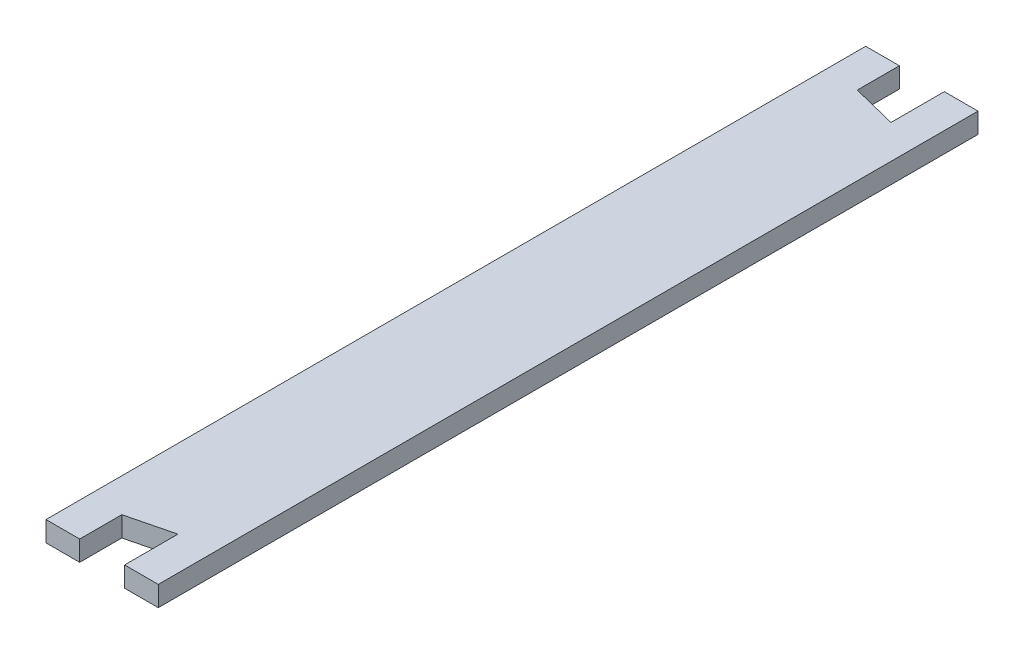
SolidWorks part; units mm, degrees
ref_plane "Front Plane" through (0, 0, 0) normal (0, 0, 1) x (1, 0, 0)
ref_plane "Top Plane" through (0, 0, 0) normal (0, 1, 0) x (1, 0, 0)
ref_plane "Right Plane" through (0, 0, 0) normal (1, 0, 0) x (0, 0, -1)
sketch "Sketch1" plane through (0, 0, 0) normal (0, 1, 0) x (1, 0, 0)
  line L0 (-450, 300) -> (-400, 300)
  line L1 (-400, 300) -> (-200, 250)
  line L2 (-200, 250) -> (200, 250) construction
  line L3 (200, 250) -> (600, 40) construction
  line L4 (600, 40) -> (1200, 40)
  line L5 (-450, -300) -> (-400, -300)
  line L6 (-400, -300) -> (-200, -250)
  line L7 (-200, -250) -> (200, -250) construction
  line L8 (200, -250) -> (600, -40) construction
  line L9 (600, -40) -> (1200, -40)
  line L10 (600, 40) -> (600, -40) construction
  line L11 (200, -250) -> (200, 250) construction
  line L12 (-200, 250) -> (-200, -250) construction
  line L13 (-400, -300) -> (-400, 300) construction
  line L14 (0, 0) -> (200, 0) construction
  line L15 (0, 250) -> (0, 0) construction
  line L16 (1200, 40) -> (1200, -40)
  line L17 (-450, 300) -> (-450, -300)
  line L18 (600, 0) -> (200, 0) construction
  line L19 (-450, 0) -> (-400, 0) construction
  line L20 (-400, 0) -> (-200, 0) construction
  line L21 (-200, 0) -> (0, 0) construction
  line L22 (-200, 250) -> (600, 40)
  line L23 (600, -40) -> (-200, -250)
  dimension "D1" = 600
  dimension "D2" = 200
  dimension "D3" = 50
  dimension "D4" = 400
  dimension "D5" = 500
  dimension "D6" = 80
  dimension "D7" = 600
  dimension "D8" = 400
extrude "Boss-Extrude1" add sketch "Sketch1" along normal blind 15
sketch "Sketch2" plane through (0, 0, 0) normal (0, 0, 1) x (1, 0, 0)
  line L0 (-450, 0) -> (-450, -40)
  line L1 (-450, -40) -> (-400, -40)
  line L2 (-400, -40) -> (-400, 0)
  line L3 (-400, 0) -> (-200, 0) construction
  line L4 (-400, 0) -> (-450, 0)
  line L5 (-440, -15) -> (-440, -40)
  line L6 (-410, -15) -> (-410, -40)
  line L7 (-425, 0) -> (-425, -15) construction
  circle A0 centre (-425, -15) radius 15
  dimension "D1" = 30
  dimension "D2" = 40
extrude "Boss-Extrude2" add sketch "Sketch2" along normal up to surface and the other way up to surface contours L4 L7 A0 L6 L1 L2 | L7 L4 L0 L1 L5 A0 region at (-444.1006, -18.2067, 0) region at (-405.8994, -18.2067, 0) up to face at (-425, 7.5, 300) other way up to face at (-425, 7.5, -300)
sketch "Sketch4" plane through (0, 0, 0) normal (0, 1, 0) x (1, 0, 0)
  line L0 (-450, 230) -> (-400, 230)
  line L1 (-450, 300) -> (-450, -300) construction
  line L2 (-400, 230) -> (-150, 167.5)
  line L3 (-150, 167.5) -> (-150, -167.5)
  line L4 (-150, -167.5) -> (-400, -230)
  line L5 (-400, -230) -> (-450, -230)
  line L6 (-400, 230) -> (-400, -230) construction
  line L7 (-200, 250) -> (-200, -250) construction
  line L9 (-200, 0) -> (-150, 0) construction
  line L10 (-400, -230) -> (-400, -300) construction
  line L11 (-400, -300) -> (-200, -250) construction
  line L12 (-450, 230) -> (-450, -230)
  line L14 (-200, 250) -> (-400, 300) construction
  line L15 (-100, 155) -> (-100, -155)
  line L16 (-100, -155) -> (520, 0)
  line L17 (520, 0) -> (-100, 155)
  line L18 (520, 0) -> (-100, 0) construction
  dimension "D1" = 460
  dimension "D2" = 300
  dimension "D3" = 50
extrude "Cut-Extrude2" cut sketch "Sketch4" against normal through all both and the other way through all
sketch "Sketch5" plane through (0, 0, 0) normal (1, 0, 0) x (0, 0, -1)
  line L0 (-300, 0) -> (-230, 0) construction
  line L1 (-285, 0) -> (-245, 0)
  line L2 (-285, 0) -> (-285, -40)
  line L3 (-285, -40) -> (-245, -40)
  line L4 (-245, 0) -> (-245, -40)
  line L5 (-300, -40) -> (-230, -40) construction
  line L6 (230, 0) -> (300, 0) construction
  line L7 (245, 0) -> (285, 0)
  line L8 (245, 0) -> (245, -40)
  line L9 (245, -40) -> (285, -40)
  line L10 (285, 0) -> (285, -40)
  line L11 (230, -40) -> (300, -40) construction
  line L12 (-300, 0) -> (-300, -40) construction
  line L13 (230, -40) -> (230, 0) construction
  line L14 (300, 0) -> (300, -40) construction
  dimension "D1" = 15
  dimension "D2" = 15
  dimension "D3" = 15
  dimension "D4" = 15
extrude "Cut-Extrude3" cut sketch "Sketch5" against normal through all
sketch "Sketch7" plane through (1200, 0, 0) normal (1, 0, 0) x (0, 0, -1)
  line L1 (-40, 15) -> (-87.5, 50)
  line L2 (-87.5, 50) -> (-87.5, 88.7)
  line L3 (-87.5, 88.7) -> (87.5, 88.7)
  line L4 (87.5, 88.7) -> (87.5, 50)
  line L5 (87.5, 50) -> (40, 15)
  line L7 (-40, 15) -> (40, 15)
  line L8 (-20, 50) -> (-20, 88.7)
  line L9 (87.5, 50) -> (-87.5, 50) construction
  line L10 (0, 88.7) -> (0, 50) construction
  line L11 (-20, 88.7) -> (20, 88.7)
  line L12 (0, 50) -> (0, 0) construction
  line L13 (20, 88.7) -> (20, 50)
  line L14 (-73, 88.7) -> (-63, 88.7)
  line L15 (-73, 88.7) -> (-73, 63.2)
  line L16 (-73, 63.2) -> (-63, 63.2)
  line L17 (-63, 88.7) -> (-63, 63.2)
  line L18 (48.5, 88.7) -> (58.5, 88.7)
  line L19 (48.5, 88.7) -> (48.5, 63.2)
  line L20 (48.5, 63.2) -> (58.5, 63.2)
  line L21 (58.5, 88.7) -> (58.5, 63.2)
  circle A0 centre (0, 50) radius 20
  line M14 (40, 15) -> (-40, 15)
  dimension "D3" = 40
  dimension "D1" = 175
  dimension "D2" = 50
  dimension "D4" = 25.5
  dimension "D5" = 10
  dimension "D6" = 63
  dimension "D7" = 48.5
  dimension "D8" = 38.7
extrude "Boss-Extrude4" add sketch "Sketch7" against normal blind 75 contours L3 L21 L20 L19 L17 L16 L15 L2 L1 L5 L4 M14 region at (1200, 34.0287, 62.6236)
sketch "Sketch8" plane through (0, 0, 0) normal (0, 0, 1) x (1, 0, 0)
  line L0 (1125, 88.7) -> (1200, 88.7) construction
  line L1 (1140, 88.7) -> (1185, 88.7)
  line L2 (1140, 88.7) -> (1140, 15)
  line L3 (1140, 15) -> (1185, 15)
  line L4 (1185, 88.7) -> (1185, 15)
  line L5 (1125, 15) -> (1200, 15) construction
  line L6 (1125, 50) -> (1125, 88.7) construction
  line L7 (1200, 50) -> (1200, 88.7) construction
  line L8 (1155, 88.7) -> (1170, 88.7) construction
  line L9 (1155, 88.7) -> (1170, 88.7)
  line L10 (1155, 88.7) -> (1155, 15)
  line L11 (1155, 15) -> (1170, 15)
  line L12 (1170, 88.7) -> (1170, 15)
  line L15 (1162.5, 50) -> (1162.5, 88.7) construction
  line L16 (1125, 50) -> (1200, 50) construction
  line L17 (1155, 88.7) -> (1170, 88.7) construction
  dimension "D1" = 15
  dimension "D2" = 15
  dimension "D3" = 15
extrude "Cut-Extrude4" cut sketch "Sketch8" against normal through all both and the other way through all contours L10 L1 L2 L3 | L1 L12 L3 L4 region at (1147.5, 51.85, 0) region at (1177.5, 51.85, 0)
fillet "Fillet1" radius 5 53 edges at (1192.5, 50, 87.5) (1162.5, 50, 87.5) (1132.5, 50, 87.5) (1192.5, 50, -87.5) (1162.5, 50, -87.5) (1132.5, 50, -87.5) (1192.5, 88.7, -87.5) (1162.5, 88.7, -87.5) (1132.5, 88.7, -87.5) (1132.5, 88.7, -58.5) (1162.5, 88.7, -58.5) (1192.5, 88.7, -58.5) (1192.5, 88.7, -48.5) (1162.5, 88.7, -48.5) (1132.5, 88.7, -48.5) (1192.5, 88.7, -20) (1162.5, 88.7, -20) (1132.5, 88.7, -20) (1192.5, 88.7, 63) (1162.5, 88.7, 63) (1132.5, 88.7, 63) (1132.5, 88.7, 87.5) (1162.5, 88.7, 87.5) (1192.5, 88.7, 87.5) (1192.5, 88.7, 73) (1162.5, 88.7, 73) (1132.5, 88.7, 73) (1192.5, 88.7, 20) (1162.5, 88.7, 20) (1132.5, 88.7, 20) (600, 7.5, 40) (600, 7.5, -40) (520, 7.5, 0) (-440, -40, -292.5) (-440, -40, -237.5) (-400, -40, -292.5) (-400, -40, -237.5) (-450, -40, -237.5) (-410, -40, -237.5) (-450, -40, -292.5) (-410, -40, -292.5) (-150, 7.5, 167.5) (-100, 7.5, 155) (-150, 7.5, -167.5) (-100, 7.5, -155) (-450, -40, 237.5) (-410, -40, 237.5) (-440, -40, 237.5) (-400, -40, 237.5) (-450, -40, 292.5) (-440, -40, 292.5) (-400, -40, 292.5) (-410, -40, 292.5)
sketch "Sketch9" plane through (0, 0, 0) normal (0, 1, 0) x (1, 0, 0)
  line L35 (-450, -300) -> (-400, -300) construction
  line L36 (-425, -300) -> (-425, -285) construction
  line L37 (-450, 0) -> (0, 0) construction
  line L38 (-437.5, -300) -> (-412.5, -300)
  line L39 (-437.5, -300) -> (-437.5, -285)
  line L56 (1140, -40) -> (1140, -85.466) construction
  line L57 (1200, -40) -> (1185, -40)
  line L58 (1200, -40) -> (1200, -25)
  line L59 (1200, -25) -> (1185, -25)
  line L60 (1185, -40) -> (1185, -25)
  line L61 (1200, 40) -> (1185, 40)
  line L62 (1200, 40) -> (1200, 25)
  line L63 (1200, 25) -> (1185, 25)
  line L64 (1185, 40) -> (1185, 25)
  line L65 (1170, 40) -> (1155, 40)
  line L66 (1170, 40) -> (1170, 25)
  line L67 (1170, 25) -> (1155, 25)
  line L68 (1155, 40) -> (1155, 25)
  line L69 (1140, 40) -> (1125, 40)
  line L70 (1140, 40) -> (1140, 25)
  line L71 (1140, 25) -> (1125, 25)
  line L72 (1125, 40) -> (1125, 25)
  line L73 (1125, -40) -> (1140, -40)
  line L74 (1125, -40) -> (1125, -25)
  line L75 (1125, -25) -> (1140, -25)
  line L76 (1140, -40) -> (1140, -25)
  line L77 (1155, -40) -> (1170, -40)
  line L78 (1155, -40) -> (1155, -25)
  line L79 (1155, -25) -> (1170, -25)
  line L80 (1170, -40) -> (1170, -25)
  line L81 (600.6453, -40) -> (1200, -40) construction
  line L82 (1200, 40) -> (600.6453, 40) construction
  line L83 (1140, 40) -> (1125, 40) construction
  line L84 (1125, 85.466) -> (1125, 40) construction
  line L85 (1140, -25) -> (1155, -25) construction
  line L86 (1170, -25) -> (1185, -25) construction
  line L87 (1185, 25) -> (1170, 25) construction
  line L88 (1155, 25) -> (1140, 25) construction
  line L89 (-437.5, -285) -> (-412.5, -285)
  line L90 (-412.5, -300) -> (-412.5, -285)
  line L92 (-410, -230) -> (-440, -230) construction
  line L93 (-437.5, -230) -> (-412.5, -230)
  line L94 (-437.5, -230) -> (-437.5, -245)
  line L95 (-437.5, -245) -> (-412.5, -245)
  line L96 (-412.5, -230) -> (-412.5, -245)
  line L97 (-425, -245) -> (-400, -245) construction
  line L98 (-425, -285) -> (-425, -245) construction
  line L99 (-425, 285) -> (-425, 245) construction
  line L100 (-425, 300) -> (-425, 285) construction
  line L101 (-450, 300) -> (-400, 300) construction
  line L102 (-412.5, 230) -> (-412.5, 245)
  line L103 (-437.5, 245) -> (-412.5, 245)
  line L104 (-437.5, 230) -> (-437.5, 245)
  line L105 (-437.5, 230) -> (-412.5, 230)
  line L106 (-412.5, 300) -> (-412.5, 285)
  line L107 (-437.5, 285) -> (-412.5, 285)
  line L108 (-437.5, 300) -> (-437.5, 285)
  line L109 (-437.5, 300) -> (-412.5, 300)
  dimension "D1" = 15
  dimension "D2" = 25
  dimension "D3" = 15
extrude "Cut-Extrude5" cut sketch "Sketch9" against normal through all both and the other way through all
sketch "Sketch10" plane through (0, 0, 0) normal (0, 0, 1) x (1, 0, 0)
  line L1 (-450, 15) -> (1200, 15)
  line L2 (-450, 15) -> (-450, 0)
  line L3 (-450, 0) -> (1200, 0)
  line L4 (1200, 15) -> (1200, 0)
  line L5 (-450, 15) -> (-450, -35) construction
  line L6 (-486.0808, 110.0266) -> (1242.84, 110.0266)
  line L7 (-486.0808, 110.0266) -> (-486.0808, -68.8272)
  line L8 (-486.0808, -68.8272) -> (1242.84, -68.8272)
  line L9 (1242.84, 110.0266) -> (1242.84, -68.8272)
  dimension "D1" = 15
extrude "Cut-Extrude6" cut sketch "Sketch10" against normal through all both and the other way through all
sketch "Sketch11" plane through (0, 0, 0) normal (0, 1, 0) x (1, 0, 0)
  line L0 (-450, -315.625) -> (323.7848, -112.5065)
  line L1 (-200, -250) -> (599.3758, -40.1638) construction
  line L2 (-450, -315.625) -> (-450, -242.5)
  line L3 (-450, -230) -> (-450, -300) construction
  line L4 (-450, -242.5) -> (308.1542, -52.9615)
  line L5 (308.1542, -52.9615) -> (323.7848, -112.5065)
  line L6 (-400, -230) -> (-153.7873, -168.4468) construction
  line L7 (-450, -242.5) -> (-450, -230)
  line L8 (-450, -230) -> (-400, -230)
  line L9 (-150, -167.5) -> (-150, -182.5)
  line L10 (-150, -182.5) -> (-135, -182.5)
  line L11 (-135, -182.5) -> (-135, -163.75)
  line L12 (-100, -155) -> (-100, -182.5)
  line L13 (-100, -182.5) -> (-115, -182.5)
  line L14 (-115, -182.5) -> (-115, -158.75)
  line L15 (-100, 148.5961) -> (-100, -148.5961) construction
  line L16 (-150, -163.5961) -> (-150, 163.5961) construction
  line L17 (309.2763, -116.315) -> (305.4678, -101.8065)
  line L18 (-601.3695, -564.0724) -> (1251.3111, -564.0724)
  line L19 (-601.3695, -564.0724) -> (-601.3695, 511.8547)
  line L20 (-601.3695, 511.8547) -> (1251.3111, 511.8547)
  line L21 (1251.3111, -564.0724) -> (1251.3111, 511.8547)
  line L22 (305.4678, -101.8065) -> (319.9763, -97.998)
  line L23 (293.6011, -56.5997) -> (297.4095, -71.1082)
  line L24 (297.4095, -71.1082) -> (311.918, -67.2997)
  line L25 (305.4678, -101.8065) -> (297.4095, -71.1082) construction
  line L26 (-758.5651, 0) -> (1550.1652, 0) construction
  line L27 (-100, -155) -> (-100, 155)
  line L28 (-100, 0) -> (-150, 0)
  line L29 (-150, 167.5) -> (-150, -167.5)
  line L30 (-115, 182.5) -> (-115, 158.75)
  line L31 (-100, 182.5) -> (-115, 182.5)
  line L32 (-100, 155) -> (-100, 182.5)
  line L33 (-135, 182.5) -> (-135, 163.75)
  line L34 (-150, 182.5) -> (-135, 182.5)
  line L35 (-150, 167.5) -> (-150, 182.5)
  line L36 (-115, 158.75) -> (-135, 163.75)
  dimension "D1" = 800
  dimension "D2" = 15
  dimension "D3" = 15
  dimension "D4" = 15
  dimension "D5" = 15
extrude "Cut-Extrude7" cut sketch "Sketch11" along normal through all contours L18 L21 L20 L19 L36 L30 L31 L32 L27 L4 L5 L0 L2 L7 L8 L29 L35 L34 L33 | L24 L23 L4 L12 L13 L14 L11 L10 L9 L2 L0 L17 L22 L5 | L8 L7 L4 | L22 L17 L0 L5 | L23 L24 L5 L4 region at (-78.7476, 0, 184.3228) region at (314.6263, 0, 107.1565) region at (-433.3333, 0, 234.1667) region at (302.7564, 0, 61.9959) region at (339.9236, 0, 22.0823)
sketch "Sketch12" plane through (0, 0, 0) normal (1, 0, 0) x (0, 0, -1)
  line L1 (-182.5, 15) -> (182.5, 15)
  line L2 (-182.5, 15) -> (-182.5, 9)
  line L3 (-182.5, 9) -> (182.5, 9)
  line L4 (182.5, 15) -> (182.5, 9)
  line L5 (182.5, 15) -> (182.5, 0) construction
  line L6 (182.5, 0) -> (-182.5, 0) construction
  point P5 (182.5, 2.9648)
  dimension "D1" = 9
extrude "Cut-Extrude8" cut sketch "Sketch12" against normal through all both and the other way through all
